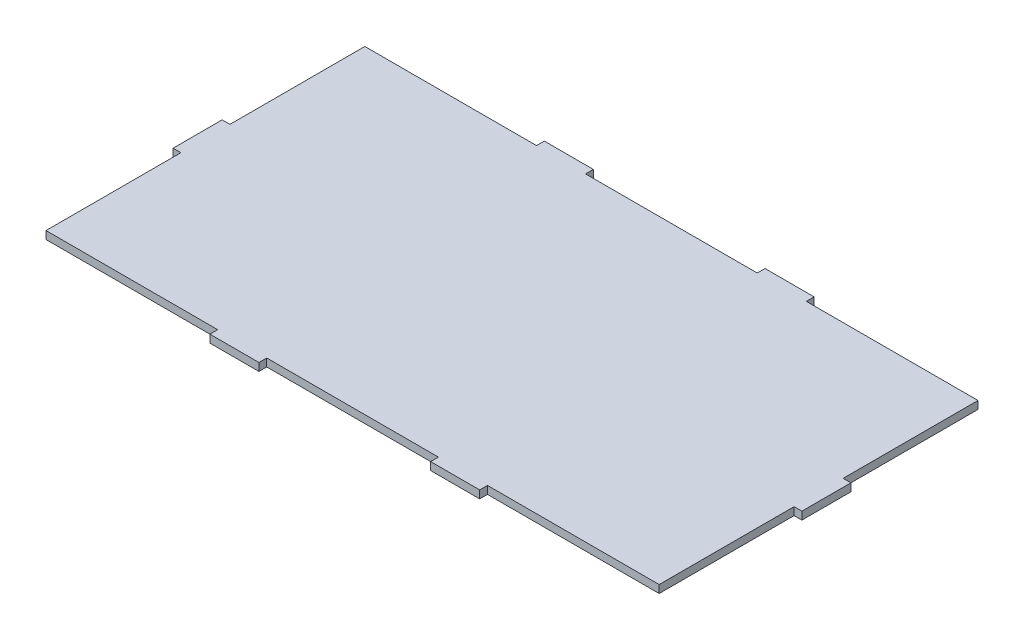
SolidWorks part; units mm, degrees
ref_plane "Plan de face" through (0, 0, 0) normal (0, 0, 1) x (1, 0, 0)
ref_plane "Plan de dessus" through (0, 0, 0) normal (0, 1, 0) x (1, 0, 0)
ref_plane "Plan de droite" through (0, 0, 0) normal (1, 0, 0) x (0, 0, -1)
sketch "Esquisse1" plane through (0, 0, 0) normal (0, 1, 0) x (1, 0, 0)
  line L1 (0, 0) -> (250, 0)
  line L2 (0, 0) -> (0, 130)
  line L3 (0, 130) -> (250, 130)
  line L4 (250, 0) -> (250, 130)
  dimension "D1" = 250
  dimension "D2" = 130
extrude "Boss.-Extru.1" add sketch "Esquisse1" along normal blind 3.175
sketch "Esquisse2" plane through (0, 3.175, 0) normal (0, 1, 0) x (1, 0, 0)
  line L0 (0, 130) -> (0, 0) construction
  line L1 (0, 75) -> (-3.175, 75)
  line L2 (0, 75) -> (0, 55)
  line L3 (0, 55) -> (-3.175, 55)
  line L4 (-3.175, 75) -> (-3.175, 55)
  line L5 (250, 130) -> (0, 130) construction
  line L6 (0, 0) -> (250, 0) construction
  line L7 (250, 0) -> (250, 130) construction
  line L8 (250, 75) -> (253.175, 75)
  line L9 (250, 75) -> (250, 55)
  line L10 (250, 55) -> (253.175, 55)
  line L11 (253.175, 75) -> (253.175, 55)
  line L13 (70, 130) -> (90, 130)
  line L14 (70, 130) -> (70, 133.175)
  line L15 (70, 133.175) -> (90, 133.175)
  line L16 (90, 130) -> (90, 133.175)
  line L17 (180, 130) -> (160, 130)
  line L18 (180, 130) -> (180, 133.175)
  line L19 (180, 133.175) -> (160, 133.175)
  line L20 (160, 130) -> (160, 133.175)
  line L21 (180, 0) -> (160, 0)
  line L22 (180, 0) -> (180, -3.175)
  line L23 (180, -3.175) -> (160, -3.175)
  line L24 (160, 0) -> (160, -3.175)
  line L25 (90, 0) -> (70, 0)
  line L26 (90, 0) -> (90, -3.175)
  line L27 (90, -3.175) -> (70, -3.175)
  line L28 (70, 0) -> (70, -3.175)
  dimension "D1" = 55
  dimension "D2" = 55
  dimension "D3" = 3.175
  dimension "D4" = 3.175
  dimension "D5" = 70
  dimension "D6" = 20
  dimension "D7" = 3.175
  dimension "D8" = 70
  dimension "D9" = 20
  dimension "D10" = 3.175
  dimension "D11" = 3.175
  dimension "D12" = 3.175
extrude "Boss.-Extru.2" add sketch "Esquisse2" against normal blind 3.175
